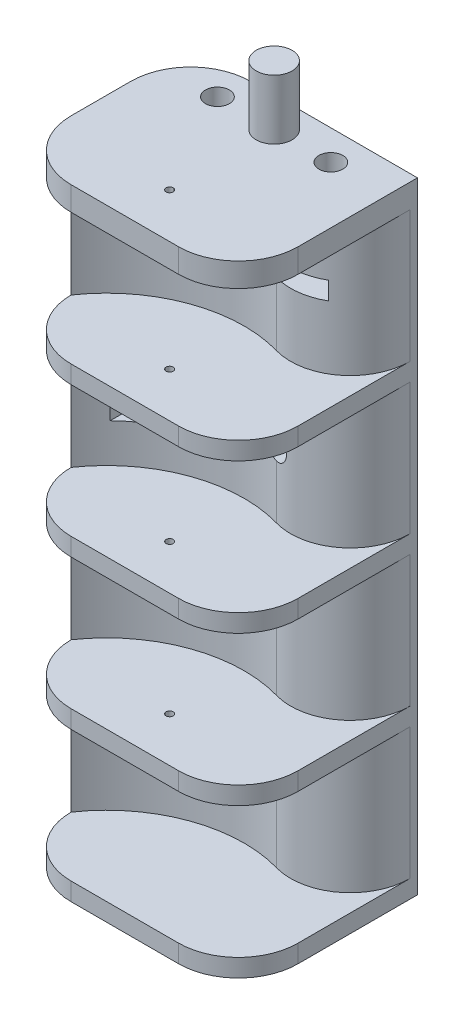
SolidWorks part; units mm, degrees
ref_plane "Alzado" through (0, 0, 0) normal (0, 0, 1) x (1, 0, 0)
ref_plane "Planta" through (0, 0, 0) normal (0, 1, 0) x (1, 0, 0)
ref_plane "Vista lateral" through (0, 0, 0) normal (1, 0, 0) x (0, 0, -1)
sketch "Croquis2" plane through (0, 0, 0) normal (0, 1, 0) x (1, 0, 0)
  line L1 (-43.1071, -17.6252) -> (-5.1071, -17.6252)
  line L2 (-43.1071, -17.6252) -> (-43.1071, -37.6252)
  line L3 (-33.1071, -47.6252) -> (-15.1071, -47.6252)
  line L4 (-5.1071, -17.6252) -> (-5.1071, -37.6252)
  arc A0 (-15.1071, -47.6252) -> (-5.1071, -37.6252) centre (-15.1071, -37.6252) ccw
  arc A1 (-33.1071, -47.6252) -> (-43.1071, -37.6252) centre (-33.1071, -37.6252) cw
  circle A2 centre (-24.1071, -40.1252) radius 0.6
  dimension "D1" = 10
extrude "Saliente-Extruir1" add sketch "Croquis2" along normal blind 4
sketch "Croquis3" plane through (0, 0, 0) normal (0, -1, 0) x (1, 0, 0)
  line L0 (-43.1071, 17.6252) -> (-5.1071, 17.6252)
  line L1 (-43.1071, 17.6252) -> (-43.1071, 37.6252)
  line L3 (-5.1071, 17.6252) -> (-5.1071, 37.6252)
  arc A0 (-43.1071, 37.6252) -> (-5.1071, 37.6252) centre (-24.1071, 50.6752) ccw
extrude "Saliente-Extruir2" add sketch "Croquis3" along normal blind 22
sketch "Croquis4" plane through (0, 4, 0) normal (0, 1, 0) x (1, 0, 0)
  circle A0 centre (-33.6071, -22.6252) radius 2
  circle A1 centre (-14.6071, -22.6252) radius 2
extrude "Cortar-Extruir1" cut sketch "Croquis4" against normal blind 15.4
sketch "Croquis5" plane through (0, 0, 17.6252) normal (0, 0, -1) x (-1, 0, 0)
  line L4 (29.1071, -8.4) -> (38.1071, -8.4)
  line L5 (38.1071, -8.4) -> (38.1071, -11.4)
  line L6 (38.1071, -11.4) -> (29.1071, -11.4)
  line L7 (29.1071, -8.4) -> (29.1071, -11.4)
  line L8 (19.1071, -8.4) -> (19.1071, -11.4)
  line L9 (10.1071, -11.4) -> (19.1071, -11.4)
  line L10 (10.1071, -8.4) -> (10.1071, -11.4)
  line L11 (19.1071, -8.4) -> (10.1071, -8.4)
extrude "Cortar-Extruir2" cut sketch "Croquis5" against normal blind 12
sketch "Croquis6" plane through (0, -22, 0) normal (0, -1, 0) x (1, 0, 0)
  line L1 (-43.1071, 17.6252) -> (-5.1071, 17.6252)
  line L2 (-43.1071, 17.6252) -> (-43.1071, 37.6252)
  line L3 (-33.1071, 47.6252) -> (-15.1071, 47.6252)
  line L4 (-5.1071, 17.6252) -> (-5.1071, 37.6252)
  circle A0 centre (-24.1071, 40.1252) radius 0.6
  arc A1 (-15.1071, 47.6252) -> (-5.1071, 37.6252) centre (-15.1071, 37.6252) cw
  arc A2 (-43.1071, 37.6252) -> (-33.1071, 47.6252) centre (-33.1071, 37.6252) cw
  dimension "D1" = 10
sketch "Croquis9" plane through (0, -22, 0) normal (0, -1, 0) x (1, 0, 0)
  line L0 (-43.1071, 37.6252) -> (-43.1071, 17.6252)
  line L1 (-43.1071, 17.6252) -> (-5.1071, 17.6252)
  line L2 (-5.1071, 17.6252) -> (-5.1071, 37.6252)
  arc A0 (-43.1071, 37.6252) -> (-5.1071, 37.6252) centre (-24.1071, 50.6752) ccw
extrude "Saliente-Extruir4" add sketch "Croquis9" along normal blind 25
extrude "Saliente-Extruir5" add sketch "Croquis6" along normal blind 3
sketch "Croquis16" plane through (0, -47, 0) normal (0, -1, 0) x (1, 0, 0)
  line L0 (-43.1071, 37.6252) -> (-43.1071, 17.6252)
  line L1 (-43.1071, 17.6252) -> (-5.1071, 17.6252)
  line L2 (-5.1071, 17.6252) -> (-5.1071, 37.6252)
  arc A0 (-5.1071, 37.6252) -> (-15.1071, 47.6252) centre (-15.1071, 37.6252) ccw construction
  arc A1 (-43.1071, 37.6252) -> (-5.1071, 37.6252) centre (-24.1071, 50.6752) ccw construction
  arc A2 (-43.1071, 37.6252) -> (-5.1071, 37.6252) centre (-24.1071, 50.6752) ccw
sketch "Croquis17" plane through (0, -47, 0) normal (0, -1, 0) x (1, 0, 0)
  line L0 (-43.1071, 17.6252) -> (-5.1071, 17.6252)
  line L1 (-5.1071, 17.6252) -> (-5.1071, 37.6252)
  line L2 (-15.1071, 47.6252) -> (-33.1071, 47.6252)
  line L3 (-43.1071, 37.6252) -> (-43.1071, 17.6252)
  arc A0 (-5.1071, 37.6252) -> (-15.1071, 47.6252) centre (-15.1071, 37.6252) ccw
  arc A1 (-33.1071, 47.6252) -> (-43.1071, 37.6252) centre (-33.1071, 37.6252) ccw
  circle A2 centre (-24.1071, 40.1252) radius 0.6
  point P14 (-13.4236, 37.6252)
  dimension "D1" = 10
extrude "Saliente-Extruir10" add sketch "Croquis16" along normal blind 25
extrude "Saliente-Extruir11" add sketch "Croquis17" along normal blind 3
sketch "Croquis18" plane through (0, -72, 0) normal (0, -1, 0) x (1, 0, 0)
  line L0 (-43.1071, 17.6252) -> (-5.1071, 17.6252)
  line L1 (-5.1071, 17.6252) -> (-5.1071, 37.6252)
  line L2 (-15.1071, 47.6252) -> (-33.1071, 47.6252)
  line L3 (-43.1071, 37.6252) -> (-43.1071, 17.6252)
  arc A0 (-5.1071, 37.6252) -> (-15.1071, 47.6252) centre (-15.1071, 37.6252) ccw
  arc A1 (-33.1071, 47.6252) -> (-43.1071, 37.6252) centre (-33.1071, 37.6252) ccw
  circle A2 centre (-24.1071, 40.1252) radius 0.6
  dimension "D1" = 10
sketch "Croquis20" plane through (0, -72, 0) normal (0, -1, 0) x (1, 0, 0)
  line L0 (-43.1071, 37.6252) -> (-43.1071, 17.6252)
  line L1 (-43.1071, 17.6252) -> (-5.1071, 17.6252)
  line L2 (-5.1071, 17.6252) -> (-5.1071, 37.6252)
  arc A0 (-43.1071, 37.6252) -> (-5.1071, 37.6252) centre (-24.1071, 50.6752) ccw
extrude "Saliente-Extruir12" add sketch "Croquis20" along normal blind 25
extrude "Saliente-Extruir13" add sketch "Croquis18" along normal blind 3
sketch "Croquis21" plane through (0, -97, 0) normal (0, -1, 0) x (1, 0, 0)
  line L0 (-43.1071, 17.6252) -> (-5.1071, 17.6252)
  line L1 (-5.1071, 17.6252) -> (-5.1071, 37.6252)
  line L2 (-15.1071, 47.6252) -> (-33.1071, 47.6252)
  line L3 (-43.1071, 37.6252) -> (-43.1071, 17.6252)
  arc A0 (-5.1071, 37.6252) -> (-15.1071, 47.6252) centre (-15.1071, 37.6252) ccw
  arc A1 (-33.1071, 47.6252) -> (-43.1071, 37.6252) centre (-33.1071, 37.6252) ccw
  dimension "D1" = 10
extrude "Saliente-Extruir14" add sketch "Croquis21" along normal blind 3
fillet "Redondeo1" radius 10 3 edges at (-5.1071, -86, 37.6252) (-5.1071, -61, 37.6252) (-5.1071, -11, 37.6252)
fillet "Redondeo2" radius 10 1 edges at (-43.1071, -48, 17.6252)
sketch "Croquis22" plane through (0, 4, 0) normal (0, 1, 0) x (1, 0, 0)
  circle A0 centre (-24.1071, -22.6252) radius 3
extrude "Saliente-Extruir15" add sketch "Croquis22" along normal blind 10
sketch "Croquis25" plane through (-5.1071, 0, 0) normal (1, 0, 0) x (0, 0, -1)
  line L6 (-35.9374, -31.5) -> (-35.9374, -40.5)
  line L7 (-35.9374, -40.5) -> (-29.9374, -40.5)
  line L8 (-35.9374, -31.5) -> (-29.9374, -31.5)
  line L9 (-29.9374, -31.5) -> (-29.9374, -40.5)
  point P17 (-32.9374, -31.5)
extrude "Cortar-Extruir3" cut sketch "Croquis25" against normal blind 35
sketch "Croquis26" plane through (-40.1071, 0, 0) normal (1, 0, 0) x (0, 0, -1)
  circle A0 centre (-32.9374, -36) radius 2.5
extrude "Cortar-Extruir4" cut sketch "Croquis26" against normal blind 3
sketch "Croquis27" plane through (0, 0, 29.9374) normal (0, 0, 1) x (1, 0, 0)
  line L0 (-40.1071, -31.5) -> (-32.733, -31.5)
  line L1 (-40.1071, -31.5) -> (-40.1071, -40.5)
  line L2 (-40.1071, -40.5) -> (-34.1693, -40.5) construction
  line L3 (-40.1071, -40.5) -> (-40.1071, -31.5) construction
  line L4 (-40.1071, -40.5) -> (-32.733, -40.5)
  line L5 (-32.733, -40.5) -> (-32.733, -31.5)
extrude "Cortar-Extruir5" cut sketch "Croquis27" against normal blind 1
sketch "Croquis29" plane through (0, 0, 28.9374) normal (0, 0, 1) x (1, 0, 0)
  line L2 (-17.8302, -47) -> (-17.8302, -25) construction
  circle A0 centre (-17.8302, -36) radius 2
extrude "Cortar-Extruir6" cut sketch "Croquis29" against normal up to surface (11.3123 mm away) up to face at (-14.6071, -9.9, 17.6252)
